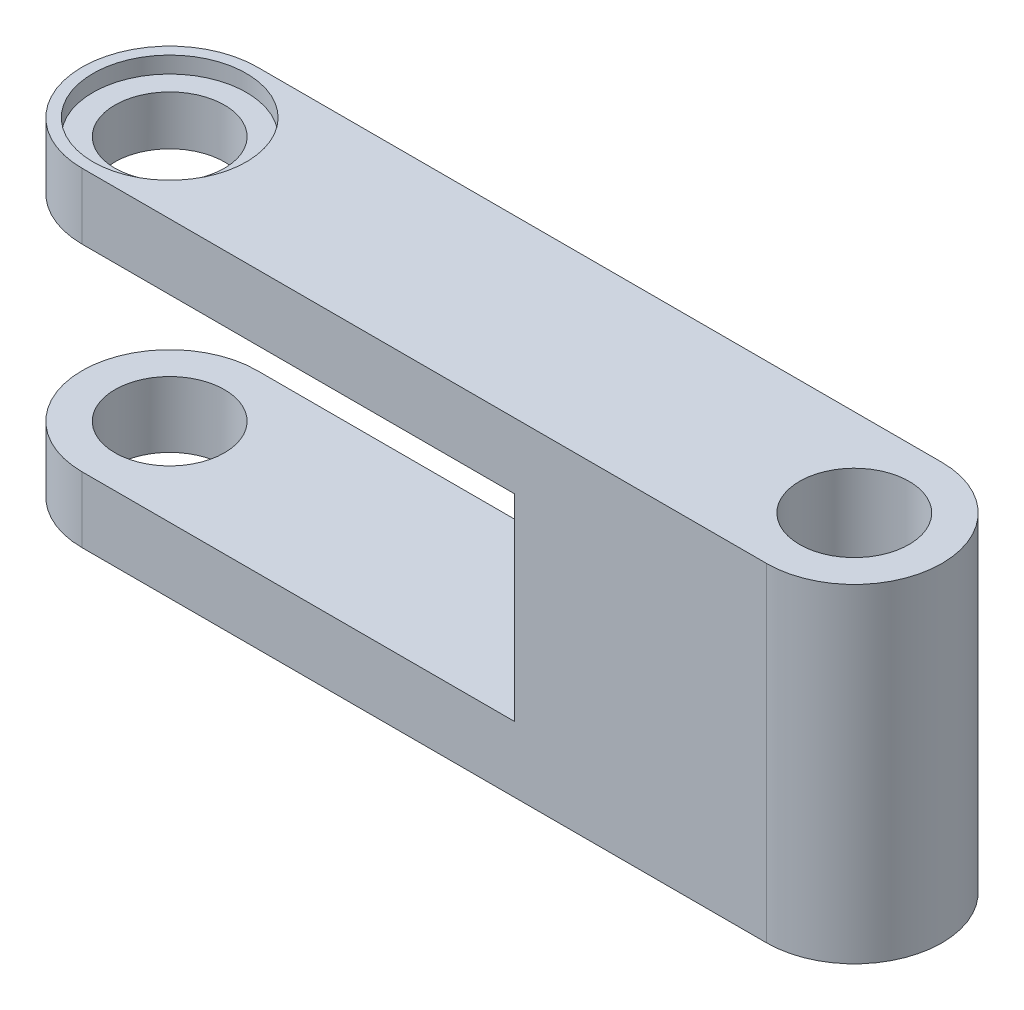
SolidWorks part; units mm, degrees
ref_plane "前视基准面" through (0, 0, 0) normal (0, 0, 1) x (1, 0, 0)
ref_plane "上视基准面" through (0, 0, 0) normal (0, 1, 0) x (1, 0, 0)
ref_plane "右视基准面" through (0, 0, 0) normal (1, 0, 0) x (0, 0, -1)
sketch "草图1" plane through (0, 0, 0) normal (0, 1, 0) x (1, 0, 0)
  line L0 (-62.5, 0) -> (62.5, 0) construction
  line L1 (-62.5, 16) -> (62.5, 16)
  line L2 (-62.5, -16) -> (62.5, -16)
  arc A0 (-62.5, 16) -> (-62.5, -16) centre (-62.5, 0) ccw
  arc A1 (62.5, -16) -> (62.5, 16) centre (62.5, 0) ccw
  point P3 (0, 0)
  point P8 (0, 0)
  dimension "D2" = 16
  dimension "D1" = 125
extrude "凸台-拉伸1" add sketch "草图1" along normal blind 60
sketch "草图2" plane through (0, 60, 0) normal (0, 1, 0) x (1, 0, 0)
  circle A0 centre (62.5, 0) radius 10
  dimension "D1" = 20
extrude "切除-拉伸1" cut sketch "草图2" against normal up to next
sketch "草图3" plane through (0, 60, 0) normal (0, 1, 0) x (1, 0, 0)
  circle A0 centre (-62.5, 0) radius 10
  dimension "D1" = 20
extrude "切除-拉伸2" cut sketch "草图3" against normal up to next
sketch "草图4" plane through (0, 60, 0) normal (0, 1, 0) x (1, 0, 0)
  circle A0 centre (-62.5, 0) radius 14
  dimension "D1" = 28
extrude "切除-拉伸3" cut sketch "草图4" against normal blind 3
ref_axis "基准轴1" through (-62.5, -14.249, 0) along (0, 1, 0)
sketch "草图6" plane through (0, 0, 16) normal (0, 0, 1) x (1, 0, 0)
  line L0 (16.5, 48) -> (16.5, 12)
  line L3 (-62.5, -14.249) -> (-62.5, 70.7632) construction
  line L4 (16.5, 48) -> (-98.5, 48)
  line L5 (16.5, 12) -> (-98.5, 12)
  line L6 (0, 30) -> (62.5, 30) construction
  line L7 (62.5, 60) -> (62.5, 0) construction
  line L8 (-98.5, 12) -> (-98.5, 48)
  point P0 (62.5, 30)
  point P3 (62.5, 30)
  point P4 (-103.7909, 48)
  dimension "D1" = 79
  dimension "D2" = 36
  dimension "D3" = 115
extrude "切除-拉伸4" cut sketch "草图6" against normal up to next
